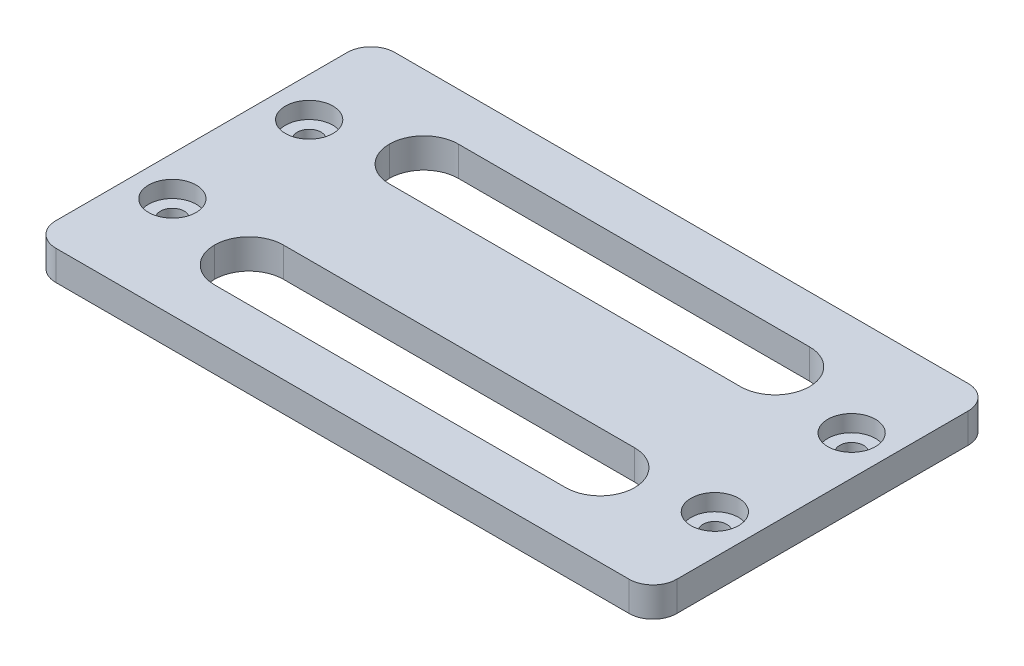
SolidWorks part; units mm, degrees
material "Custom Plastic"
ref_plane "Front Plane" through (0, 0, 0) normal (0, 0, 1) x (1, 0, 0)
ref_plane "Top Plane" through (0, 0, 0) normal (0, 1, 0) x (1, 0, 0)
ref_plane "Right Plane" through (0, 0, 0) normal (1, 0, 0) x (0, 0, -1)
sketch "Sketch1" plane through (0, 0, 0) normal (0, 1, 0) x (1, 0, 0)
  line L0 (-35.9391, 2.55) -> (38.4915, 2.55) construction
  line L1 (-26.1, -11.7) -> (26.1, -11.7)
  line L2 (-26.1, -11.7) -> (-26.1, 16.8)
  line L3 (-26.1, 16.8) -> (26.1, 16.8)
  line L4 (26.1, -11.7) -> (26.1, 16.8)
  line L5 (-26.1, -11.7) -> (26.1, 16.8) construction
  line L6 (-26.1, 16.8) -> (26.1, -11.7) construction
  line L7 (0, 29.6091) -> (0, -31.2199) construction
  line L8 (0, 16.8) -> (0, 0) construction
  line L10 (-17.6603, -1.9) -> (17.6603, -1.9)
  line L11 (-17.6603, 7) -> (17.6603, 7)
  line L12 (-17.6603, 7) -> (-17.6603, 12.8)
  line L13 (-17.6603, 12.8) -> (17.6603, 12.8)
  line L14 (17.6603, 7) -> (17.6603, 12.8)
  line L23 (17.6603, -1.9) -> (17.6603, -7.7)
  line L24 (-17.6603, -7.7) -> (17.6603, -7.7)
  line L25 (-17.6603, -1.9) -> (-17.6603, -7.7)
  circle A0 centre (-22.8, -3.2) radius 1
  circle A1 centre (22.8, -3.2) radius 1
  circle A2 centre (22.8, 8.3) radius 1
  circle A3 centre (-22.8, 8.3) radius 1
  point P0 (0, 0)
  dimension "D3" = 2
  dimension "D1" = 28.5
  dimension "D2" = 52.2
  dimension "D4" = 8.5
  dimension "D5" = 8.5
  dimension "D7" = 4
  dimension "D9" = 5.8
  dimension "D10" = 35.3206
  dimension "D11" = 8.4397
extrude "Boss-Extrude1" add sketch "Sketch1" along normal blind 2.5
fillet "Fillet1" radius 2 4 edges at (26.1, 1.25, -16.8) (26.1, 1.25, 11.7) (-26.1, 1.25, 11.7) (-26.1, 1.25, -16.8)
fillet "Fillet2" radius 2.9 8 edges at (17.6603, 1.25, -7) (17.6603, 1.25, -12.8) (17.6603, 1.25, 7.7) (17.6603, 1.25, 1.9) (-17.6603, 1.25, 7.7) (-17.6603, 1.25, 1.9) (-17.6603, 1.25, -7) (-17.6603, 1.25, -12.8)
sketch "Sketch4" plane through (0, 2.5, 0) normal (0, 1, 0) x (1, 0, 0)
  circle A0 centre (-22.8, 8.3) radius 2
  circle A1 centre (-22.8, -3.2) radius 2
  circle A2 centre (22.8, -3.2) radius 2
  circle A3 centre (22.8, 8.3) radius 2
  dimension "D1" = 4
  dimension "D2" = 4
  dimension "D3" = 4
  dimension "D4" = 4
extrude "Cut-Extrude1" cut sketch "Sketch4" against normal blind 1.4
